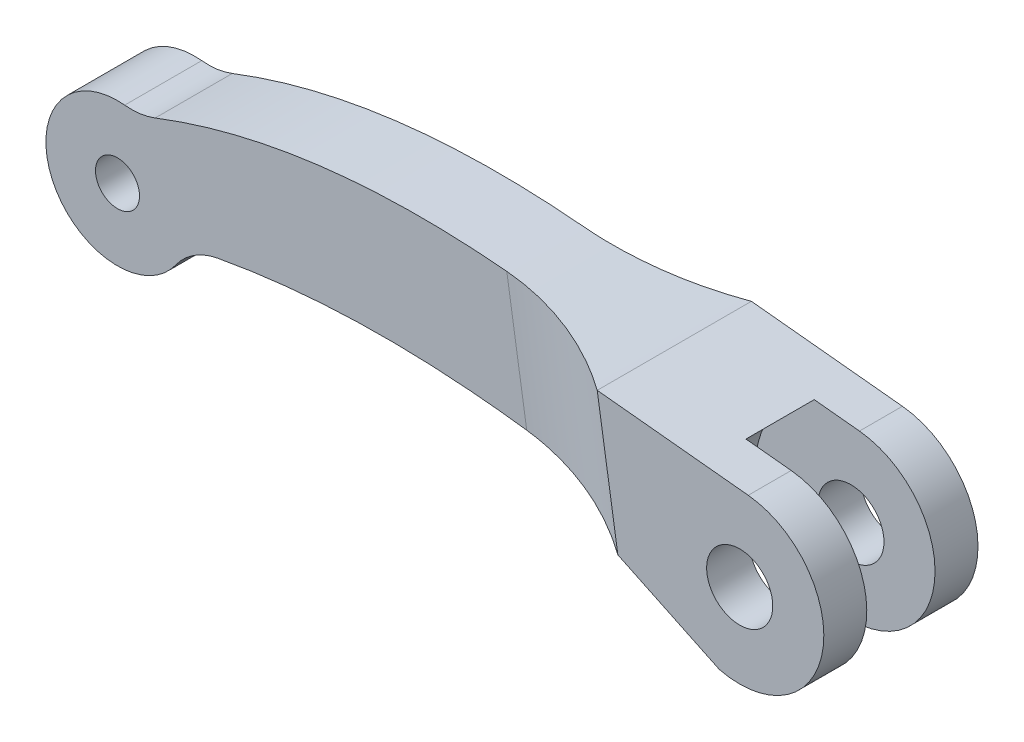
SolidWorks part; units mm, degrees
ref_plane "Спереди" through (0, 0, 0) normal (0, 0, 1) x (1, 0, 0)
ref_plane "Сверху" through (0, 0, 0) normal (0, 1, 0) x (1, 0, 0)
ref_plane "Справа" through (0, 0, 0) normal (1, 0, 0) x (0, 0, -1)
sketch "Sketch1" plane through (0, 0, 0) normal (0, 0, 1) x (1, 0, 0)
  line L2 (0, 0) -> (1, 0) construction
  line L3 (3.1038, -0.9691) -> (14.5105, 1.5965) construction
  line L4 (14.5105, 1.5965) -> (28.4491, -2.568) construction
  line L5 (0.9429, 3.1119) -> (12.7162, 8.0725) construction
  line L6 (12.7162, 8.0725) -> (29.5304, 2.963) construction
  circle A0 centre (0, 0) radius 1
  arc A2 (28.4491, -2.568) -> (29.5304, 2.963) centre (30, 0) ccw
  circle A3 centre (30, 0) radius 1.5
  arc A4 (0.9429, 3.1119) -> (3.1038, -0.9691) centre (0, 0) ccw
  spline S0 degree 2 poles (3.1038, -0.9691) (14.5105, 1.5965) (28.4491, -2.568) knots 0 0 0 1 1 1
  spline S1 degree 2 poles (0.9429, 3.1119) (12.7162, 8.0725) (29.5304, 2.963) knots 0 0 0 1 1 1
  dimension "D4" = 2
  dimension "D6" = 3
  dimension "D7" = 6
  dimension "D2" = 30
extrude "Boss-Extrude1" add sketch "Sketch1" along normal mid plane 3.5
fillet "Fillet1" radius 3 1 edges at (29.5304, 2.963, 0)
sketch "Sketch2" plane through (0, 0, 0) normal (0, 0, 1) x (1, 0, 0)
  line L0 (30.3874, 3.7998) -> (23.5309, 4.4988)
  line L1 (23.5309, 4.4988) -> (24.468, -1.5037)
  line L2 (24.468, -1.5037) -> (29.0737, -3.7055)
  circle A0 centre (30, 0) radius 1.5
  circle A1 centre (30, 0) radius 1.5 construction
  arc A2 (29.0737, -3.7055) -> (30.3874, 3.7998) centre (30, 0) ccw
  parabola Q0 (29.002, 3.1215) -> (0.9429, 3.1119) focus (5.6866, -10.5839) apex (-0.7735, 2.3218) construction
  parabola Q1 (3.1038, -0.9691) -> (28.4491, -2.568) focus (4.6731, -19.9146) apex (-1.8929, -2.4613) construction
  parabola Q2 (3.1038, -0.9691) -> (28.4491, -2.568) focus (4.6731, -19.9146) apex (-1.8929, -2.4613) construction
extrude "Boss-Extrude2" add sketch "Sketch2" along normal mid plane 7
sketch "Sketch3" plane through (0, 0, 0) normal (0, 0, 1) x (1, 0, 0)
  circle A0 centre (30, 0) radius 4.342
extrude "Cut-Extrude1" cut sketch "Sketch3" against normal mid plane 3.1
fillet "Fillet2" radius 10 2 edges at (23.9995, 1.4976, -1.75) (23.9995, 1.4976, 1.75)
fillet "Fillet3" radius 3 2 edges at (0.9429, 3.1119, 0) (3.1038, -0.9691, 0)
